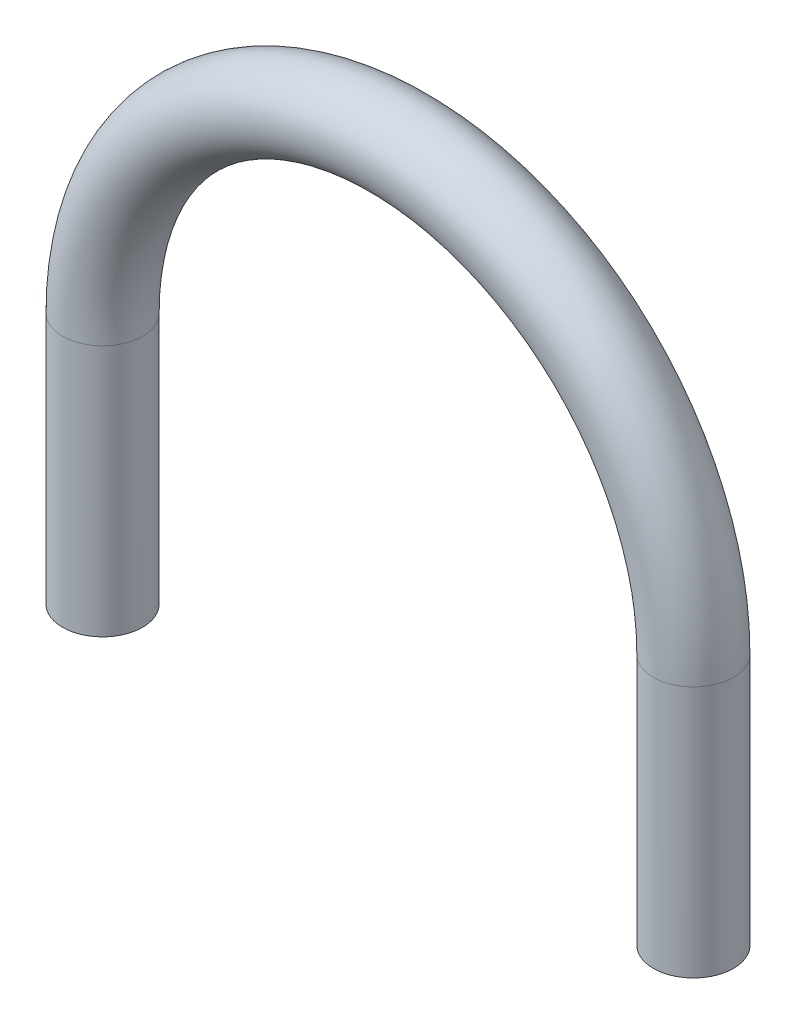
SolidWorks part; units mm, degrees
ref_plane "Plan de face" through (0, 0, 0) normal (0, 0, 1) x (1, 0, 0)
ref_plane "Plan de dessus" through (0, 0, 0) normal (0, 1, 0) x (1, 0, 0)
ref_plane "Plan de droite" through (0, 0, 0) normal (1, 0, 0) x (0, 0, -1)
sketch "Esquisse1" plane through (0, 0, 0) normal (0, 0, 1) x (1, 0, 0)
  line L0 (-23.44, -20) -> (-23.44, 0)
  line L1 (23.44, -20) -> (23.44, 0)
  arc A0 (-23.44, 0) -> (23.44, 0) centre (0, 0) cw
sweep "Balayage3" add path "Esquisse1" circular profile diameter 6.35 parameters "D3"=6.35
